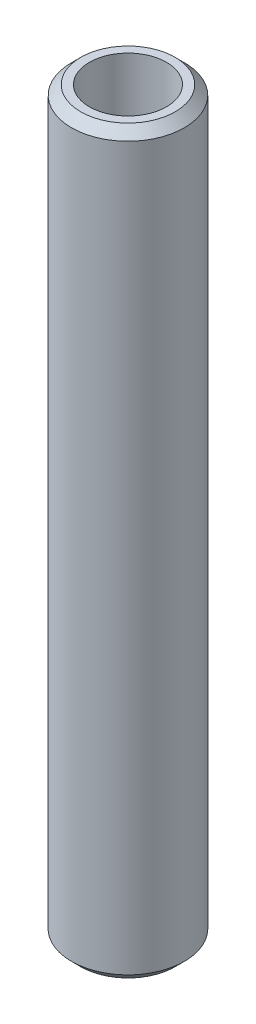
SolidWorks part; units mm, degrees
ref_plane "Front Plane" through (0, 0, 0) normal (0, 0, 1) x (1, 0, 0)
ref_plane "Top Plane" through (0, 0, 0) normal (0, 1, 0) x (1, 0, 0)
ref_plane "Right Plane" through (0, 0, 0) normal (1, 0, 0) x (0, 0, -1)
sketch "Sketch1" plane through (0, 0, 0) normal (0, 1, 0) x (1, 0, 0)
  circle A0 centre (0, 0) radius 22.5
  dimension "SHAFT_OD" = 45
extrude "Boss-Extrude1" add sketch "Sketch1" along normal blind 295.1459
sketch "Sketch2" plane through (0, 0, 0) normal (0, 1, 0) x (1, 0, 0)
  circle A0 centre (0, 0) radius 15.3809
  dimension "BORE_D" = 30.7617
extrude "Cut-Extrude1" cut sketch "Sketch2" along normal through all
chamfer "Chamfer1" distance 3.6746 angle 45 2 edges at (0, 295.1459, 22.5) (0, 0, 22.5)
